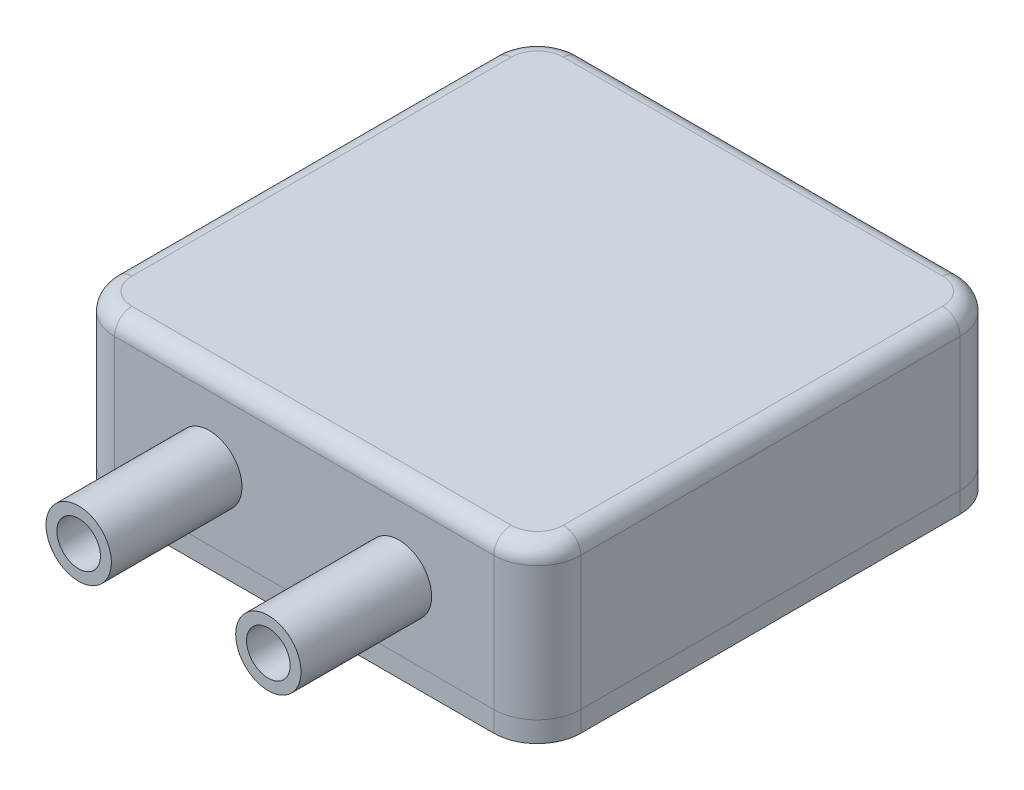
SolidWorks part; units mm, degrees
ref_plane "Front Plane" through (0, 0, 0) normal (0, 0, 1) x (1, 0, 0)
ref_plane "Top Plane" through (0, 0, 0) normal (0, 1, 0) x (1, 0, 0)
ref_plane "Right Plane" through (0, 0, 0) normal (1, 0, 0) x (0, 0, -1)
sketch "Sketch1" plane through (0, 0, 0) normal (0, 1, 0) x (1, 0, 0)
  line L1 (-34, 34) -> (34, 34)
  line L2 (-34, 34) -> (-34, -34)
  line L3 (-34, -34) -> (34, -34)
  line L4 (34, 34) -> (34, -34)
  line L5 (-34, 34) -> (34, -34) construction
  line L6 (-34, -34) -> (34, 34) construction
  point P0 (0, 0)
  dimension "D1" = 68
  dimension "D2" = 68
extrude "Boss-Extrude1" add sketch "Sketch1" along normal blind 22
fillet "Fillet1" radius 2.54 4 edges at (-34, 22, 0) (0, 22, -34) (34, 22, 0) (0, 22, 34)
fillet "Fillet2" radius 6.35 8 edges at (33.2561, 21.2561, 33.2561) (-33.2561, 21.2561, 33.2561) (-33.2561, 21.2561, -33.2561) (33.2561, 21.2561, -33.2561) (34, 9.73, -34) (-34, 9.73, -34) (-34, 9.73, 34) (34, 9.73, 34)
sketch "Sketch2" plane through (0, 0, 34) normal (0, 0, 1) x (1, 0, 0)
  line L0 (-27.65, 9.73) -> (27.65, 9.73) construction
  line L1 (-27.65, 19.46) -> (-27.65, 0) construction
  line L2 (27.65, 0) -> (27.65, 19.46) construction
  line L3 (0, 19.46) -> (0, 0) construction
  line L4 (27.65, 19.46) -> (-27.65, 19.46) construction
  line L5 (-27.65, 0) -> (27.65, 0) construction
  circle A0 centre (-13.8303, 9.73) radius 3.175
  circle A1 centre (-13.8303, 9.73) radius 4.7625
  circle A2 centre (13.8303, 9.73) radius 4.7625
  circle A3 centre (13.8303, 9.73) radius 3.175
  dimension "D1" = 9.525
  dimension "D2" = 6.35
  dimension "D3" = 13.8303
  dimension "D4" = 13.8303
extrude "Boss-Extrude2" add sketch "Sketch2" along normal blind 19.05
sketch "Sketch3" plane through (0, 0, 0) normal (0, -1, 0) x (1, 0, 0)
  line L1 (-34, 34) -> (34, 34)
  line L2 (-34, 34) -> (-34, -34)
  line L3 (-34, -34) -> (34, -34)
  line L4 (34, 34) -> (34, -34)
  line L5 (-34, 34) -> (34, -34) construction
  line L6 (-34, -34) -> (34, 34) construction
  point P0 (0, 0)
  dimension "D1" = 68
  dimension "D2" = 68
extrude "Boss-Extrude3" add sketch "Sketch3" along normal blind 3 separate body
fillet "Fillet3" radius 6.35 4 edges at (-34, -1.5, -34) (34, -1.5, -34) (34, -1.5, 34) (-34, -1.5, 34)
